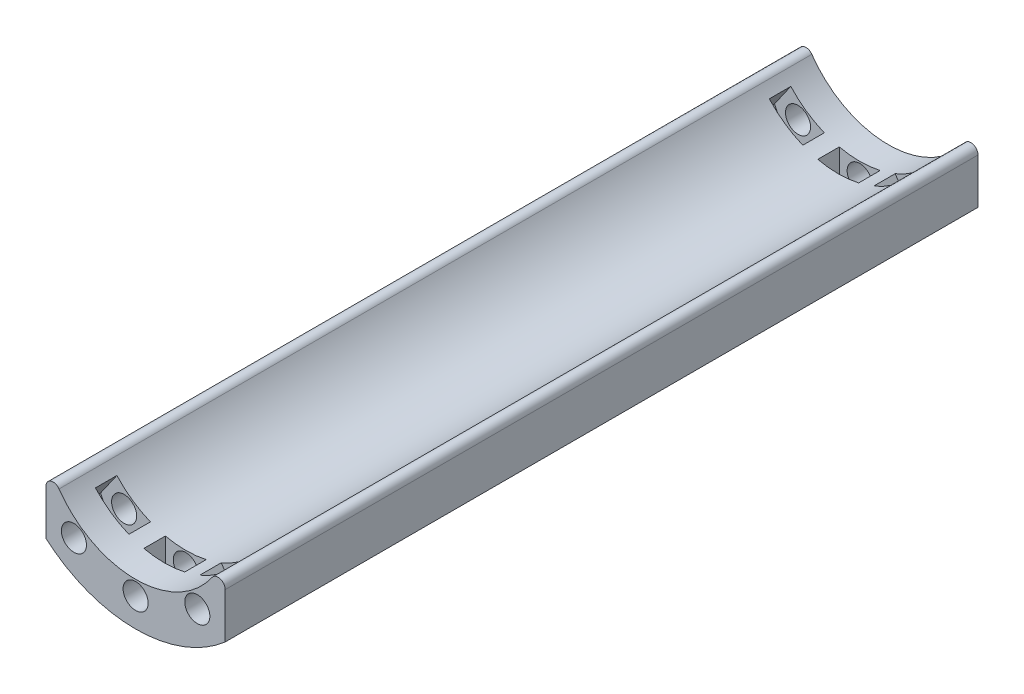
SolidWorks part; units mm, degrees
ref_plane "Front Plane" through (0, 0, 0) normal (0, 0, 1) x (1, 0, 0)
ref_plane "Top Plane" through (0, 0, 0) normal (0, 1, 0) x (1, 0, 0)
ref_plane "Right Plane" through (0, 0, 0) normal (1, 0, 0) x (0, 0, -1)
sketch "Sketch1" plane through (0, 0, 0) normal (0, 0, 1) x (1, 0, 0)
  line L2 (-18.375, -14.3091) -> (-18.375, 159.3091)
  line L3 (-43.375, 159.3091) -> (-43.375, -14.3091)
  line L4 (-18.375, -14.3091) -> (-18.375, 159.3091)
  line L5 (-43.375, 159.3091) -> (-43.375, -14.3091)
  circle A0 centre (-30.875, 0) radius 13
  arc A2 (-18.375, 159.3091) -> (-43.375, 159.3091) centre (-30.875, 145) ccw
  arc A3 (-43.375, -14.3091) -> (-18.375, -14.3091) centre (-30.875, 0) ccw
  arc A4 (-18.375, 159.3091) -> (-43.375, 159.3091) centre (-30.875, 145) ccw
  arc A5 (-43.375, -14.3091) -> (-18.375, -14.3091) centre (-30.875, 0) ccw
  dimension "D2" = 6
  dimension "D1" = 0
extrude "Boss-Extrude1" add sketch "Sketch1" along normal up to surface (105 mm away) contours L5 A5 L4 A0 region at (-30.875, -13.7148, 0)
sketch "Sketch3" plane through (0, 0, 0) normal (0, 0, -1) x (-1, 0, 0)
  circle A1 centre (30.875, -15) radius 1.75 construction
  circle A2 centre (39.4786, -12.2873) radius 1.75 construction
  circle A3 centre (22.2714, -12.2873) radius 1.75
  circle A4 centre (30.875, -15) radius 1.75
  circle A5 centre (39.4786, -12.2873) radius 1.75
  circle A6 centre (22.2714, -12.2873) radius 1.75 construction
  circle A7 centre (22.2714, -12.2873) radius 1.75 construction
extrude "Cut-Extrude1" cut sketch "Sketch3" against normal blind 15 contours A3 | A4 | A5 region at (-22.2714, -12.2873, 0) region at (-30.875, -15, 0) region at (-39.4786, -12.2873, 0)
ref_plane "Plane1" through (0, 0, 4) normal (0, 0, -1) x (-1, 0, 0)
ref_plane "Plane2" through (0, 0, 52.5) normal (0, 0, -1) x (-1, 0, 0)
sketch "Sketch4" plane through (0, 0, 4) normal (0, 0, -1) x (-1, 0, 0)
  line L0 (20.8806, -9.3047) -> (21.2653, -8.7552)
  line L1 (30.875, -18.2909) -> (33.725, -16.6454)
  line L2 (33.725, -16.6454) -> (33.725, -13.3546)
  line L3 (33.725, -13.3546) -> (30.875, -11.7091)
  line L4 (30.875, -11.7091) -> (28.025, -13.3546)
  line L5 (28.025, -13.3546) -> (28.025, -16.6454)
  line L6 (28.025, -16.6454) -> (30.875, -18.2909)
  line L7 (25.5497, -12.5741) -> (25.9345, -12.0246)
  line L8 (24.1589, -9.5915) -> (20.3838, -14.983) construction
  line L9 (20.3838, -14.983) -> (23.6621, -15.2698)
  line L10 (23.6621, -15.2698) -> (25.5497, -12.5741)
  line L11 (25.5497, -12.5741) -> (24.1589, -9.5915)
  line L12 (24.1589, -9.5915) -> (20.8806, -9.3047)
  line L13 (20.8806, -9.3047) -> (18.993, -12.0005)
  line L14 (18.993, -12.0005) -> (20.3838, -14.983)
  line L15 (30.875, 0) -> (24.1589, -9.5915) construction
  line L16 (30.875, 0) -> (30.875, -19) construction
  line L17 (28.025, -13.3546) -> (28.025, -12.6837)
  line L18 (33.725, -13.3546) -> (33.725, -12.6837)
  line L19 (36.2003, -12.5741) -> (37.5911, -9.5915)
  line L20 (37.5911, -9.5915) -> (40.8694, -9.3047)
  line L21 (40.8694, -9.3047) -> (42.757, -12.0005)
  line L22 (42.757, -12.0005) -> (41.3662, -14.983)
  line L23 (41.3662, -14.983) -> (38.0879, -15.2698)
  line L24 (38.0879, -15.2698) -> (36.2003, -12.5741)
  line L25 (36.2003, -12.5741) -> (35.8155, -12.0246)
  line L26 (40.8694, -9.3047) -> (40.4847, -8.7552)
  line L27 (18.375, -14.3091) -> (18.375, -3.5707) construction
  line L28 (18.375, -14.3091) -> (18.375, -3.5707)
  line L29 (43.375, -3.5707) -> (43.375, -14.3091) construction
  line L30 (43.375, -3.5707) -> (43.375, -14.3091)
  circle A0 centre (30.875, -15) radius 2.85 construction
  arc A1 (18.375, -14.3091) -> (43.375, -14.3091) centre (30.875, 0) ccw construction
  arc A2 (18.375, -14.3091) -> (43.375, -14.3091) centre (30.875, 0) ccw
  arc A3 (18.375, -3.5707) -> (43.375, -3.5707) centre (30.875, 0) ccw construction
  arc A4 (18.375, -3.5707) -> (43.375, -3.5707) centre (30.875, 0) ccw
  circle A5 centre (22.2714, -12.2873) radius 2.85 construction
  circle A6 centre (22.2714, -12.2873) radius 1.75 construction
  circle A7 centre (30.875, -15) radius 1.75 construction
  dimension "D1" = 5.7
extrude "Cut-Extrude2" cut sketch "Sketch4" against normal blind 3 contours A4 L12 L13 L14 A2 L9 L10 L11 | A4 L0 L12 | A4 L11 L7 | A4 L4 L5 L6 A2 L1 L2 L3 | A4 L17 L4 | A4 L3 L18 | A4 L19 L24 L23 A2 L22 L21 L20 | A4 L25 L19 | A4 L20 L26 region at (-21.3409, -9.1521, 4) region at (-22.1244, -12.4971, 4) region at (-25.5357, -12.0894, 4) region at (-28.3145, -12.9655, 4) region at (-30.875, -15.2561, 4) region at (-40.4091, -9.1521, 4) region at (-33.4355, -12.9655, 4) region at (-39.6256, -12.4971, 4) region at (-36.2143, -12.0894, 4)
mirror "Mirror1" about plane through (0, 0, 52.5) normal (0, 0, -1) of "Cut-Extrude1", "Cut-Extrude2"
fillet "Fillet1" radius 1 2 edges at (-43.375, -3.5707, 52.5) (-18.375, -3.5707, 52.5)
ref_plane "Plane3" through (0, -19, 0) normal (0, -1, 0) x (-1, 0, 0)
